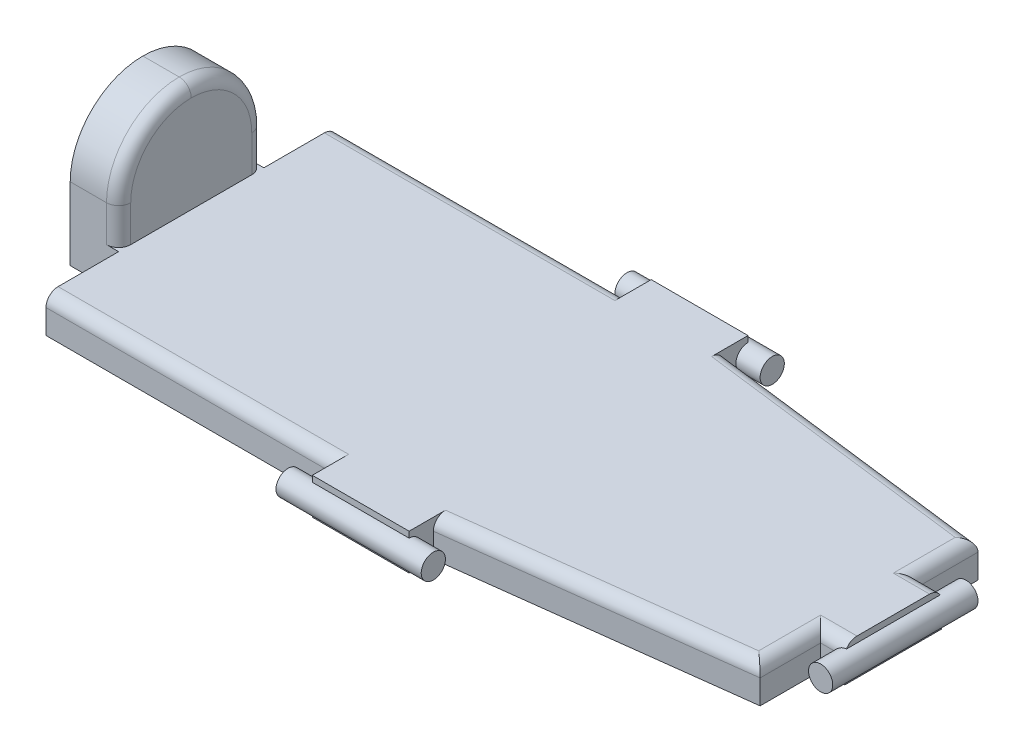
SolidWorks part; units mm, degrees
ref_plane "Front Plane" through (0, 0, 0) normal (0, 0, 1) x (1, 0, 0)
ref_plane "Top Plane" through (0, 0, 0) normal (0, 1, 0) x (1, 0, 0)
ref_plane "Right Plane" through (0, 0, 0) normal (1, 0, 0) x (0, 0, -1)
sketch "Sketch1" plane through (0, 0, 0) normal (0, 1, 0) x (1, 0, 0)
  line L0 (0, 0) -> (300, 0)
  line L1 (0, 0) -> (0, -30)
  line L2 (0, -30) -> (20, -30)
  line L3 (20, -30) -> (20, -60)
  line L4 (300, 0) -> (300, -45)
  line L5 (20, -60) -> (180, -60)
  line L6 (180, -60) -> (300, -45)
  dimension "D1" = 300
  dimension "D2" = 30
  dimension "D3" = 20
  dimension "D4" = 30
  dimension "D5" = 45
  dimension "D6" = 160
extrude "Boss-Extrude2" add sketch "Sketch1" along normal blind 15
sketch "Sketch3" plane through (0, 0, 60) normal (0, 0, 1) x (1, 0, 0)
  line L0 (20, 15) -> (180, 15) construction
  line L1 (180, 0) -> (140, 0)
  line L2 (180, 0) -> (180, 15)
  line L3 (180, 15) -> (140, 15)
  line L4 (140, 0) -> (140, 15)
  dimension "D1" = 40
extrude "Boss-Extrude3" add sketch "Sketch3" along normal blind 10
sketch "Sketch4" plane through (180, 0, 0) normal (1, 0, 0) x (0, 0, -1)
  line L0 (-70, 0) -> (-70, 15) construction
  circle A0 centre (-70, 7.5) radius 5
  dimension "D1" = 10
extrude "Boss-Extrude4" add sketch "Sketch4" along normal blind 10 and the other way blind 50
sketch "Sketch5" plane through (300, 0, 0) normal (1, 0, 0) x (0, 0, -1)
  line L0 (-45, 0) -> (0, 0) construction
  line L1 (0, 15) -> (-20, 15)
  line L2 (0, 15) -> (0, 0)
  line L3 (0, 0) -> (-20, 0)
  line L4 (-20, 15) -> (-20, 0)
  dimension "D1" = 20
extrude "Boss-Extrude5" add sketch "Sketch5" along normal blind 10
sketch "Sketch6" plane through (0, 0, 20) normal (0, 0, 1) x (1, 0, 0)
  line L0 (310, 15) -> (310, 0) construction
  circle A0 centre (310, 7.5) radius 5
  dimension "D1" = 10
extrude "Boss-Extrude6" add sketch "Sketch6" along normal blind 10 and the other way blind 20
mirror "Mirror1" about plane through (0, 15, 0) normal (0, 0, 1) of "Boss-Extrude6", "Boss-Extrude5", "Boss-Extrude4", "Boss-Extrude3", "Boss-Extrude2"
sketch "Sketch7" plane through (0, 0, 0) normal (0, 1, 0) x (1, 0, 0)
  line L1 (0, 30) -> (20, 30)
  line L2 (0, 30) -> (0, -30)
  line L3 (0, -30) -> (20, -30)
  line L4 (20, 30) -> (20, -30)
extrude "Boss-Extrude7" add sketch "Sketch7" along normal blind 60
sketch "Sketch9" plane through (0, 0, 0) normal (-1, 0, 0) x (0, 0, 1)
  line L0 (-30, 60) -> (30, 60) construction
  circle A0 centre (0, 35) radius 15
  dimension "D1" = 30
  dimension "D2" = 25
extrude "Cut-Extrude1" cut sketch "Sketch9" against normal blind 5
sketch "Sketch10" plane through (5, 0, 0) normal (-1, 0, 0) x (0, 0, 1)
  circle A0 centre (0, 35) radius 18
  dimension "D1" = 36
extrude "Cut-Extrude2" cut sketch "Sketch10" against normal blind 5
fillet "Fillet1" radius 30 2 edges at (10, 60, -30) (10, 60, 30)
fillet "Fillet2" radius 5 12 edges at (20, 22.5, -30) (20, 51.2132, -21.2132) (20, 22.5, 30) (240, 15, -52.5) (305, 15, -20) (240, 15, 52.5) (20, 51.2132, 21.2132)
